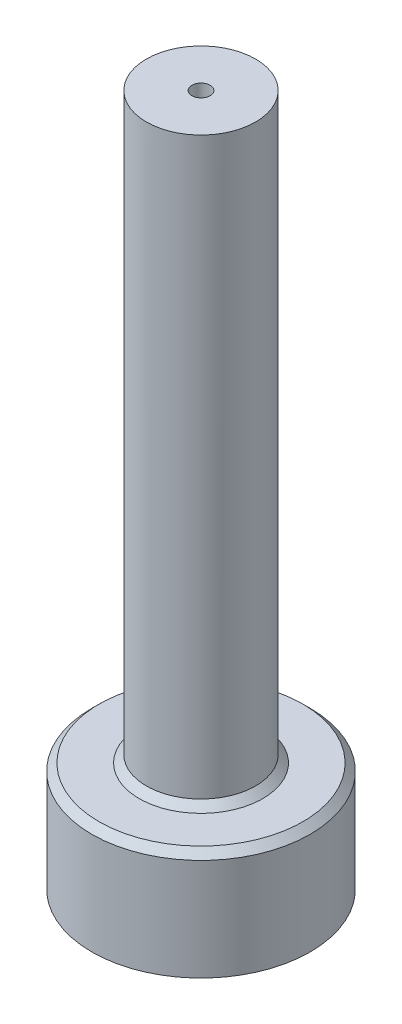
SolidWorks part; units mm, degrees
material "Nickel"
ref_plane "Front Plane" through (0, 0, 0) normal (0, 0, 1) x (1, 0, 0)
ref_plane "Top Plane" through (0, 0, 0) normal (0, 1, 0) x (1, 0, 0)
ref_plane "Right Plane" through (0, 0, 0) normal (1, 0, 0) x (0, 0, -1)
sketch "Sketch2" plane through (0, 0, 0) normal (0, 1, 0) x (1, 0, 0)
  circle A0 centre (0, 0) radius 15
extrude "Boss-Extrude1" add sketch "Sketch2" along normal blind 190
sketch "Sketch3" plane through (0, 0, 0) normal (0, -1, 0) x (1, 0, 0)
  circle A0 centre (0, 0) radius 30
extrude "Boss-Extrude2" add sketch "Sketch3" against normal blind 30
sketch "Sketch7" plane through (0, 190, 0) normal (0, 1, 0) x (1, 0, 0)
  circle A0 centre (0, 0) radius 2.5
chamfer "Chamfer1" distance 2 angle 45 1 edges at (0, 30, -15)
chamfer "Chamfer2" distance 2 angle 45 1 edges at (0, 30, -30)
sketch "Sketch9" plane through (0, 30, 0) normal (0, 1, 0) x (1, 0, 0)
  circle A0 centre (0, 0) radius 2
loft "Cut-Loft1" cut profiles "Sketch7", "Sketch9" connector at (-0.0911, 190, 2.4983) connector at (-0.4436, 30, 1.9502)
sketch "Sketch10" plane through (0, 30, 0) normal (0, 1, 0) x (1, 0, 0)
  circle A0 centre (0, 0) radius 2
sketch "Sketch11" plane through (0, 0, 0) normal (0, -1, 0) x (1, 0, 0)
  circle A0 centre (0, 0) radius 22.5
loft "Cut-Loft3" cut profiles "Sketch10", "Sketch11" connector at (1.8641, 30, -0.7246) connector at (19.5582, 0, -11.1233)
